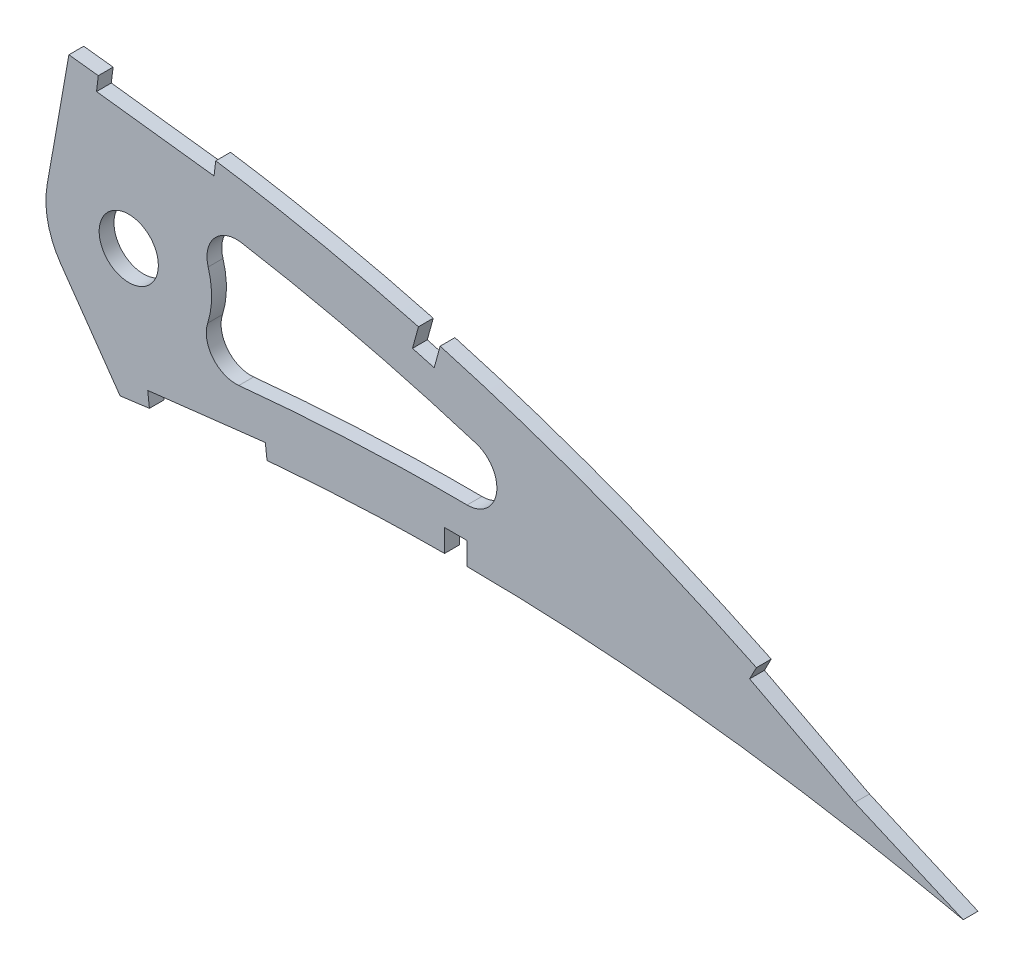
SolidWorks part; units mm, degrees
material "Plywood"
ref_plane "Front Plane" through (0, 0, 0) normal (0, 0, 1) x (1, 0, 0)
ref_plane "Top Plane" through (0, 0, 0) normal (0, 1, 0) x (1, 0, 0)
ref_plane "Right Plane" through (0, 0, 0) normal (1, 0, 0) x (0, 0, -1)
curve "Curve1"
  spline degree 3 poles (554.3197, 0.8642, 0) (554.2772, 0.8904, 0) (554.1075, 0.9953, 0) (553.7252, 1.2298, 0) (553.0885, 1.6204, 0) (552.1972, 2.1644, 0) (551.0519, 2.8603, 0) (549.6522, 3.7033, 0) (547.9988, 4.6906, 0) (546.0922, 5.8176, 0) (543.9326, 7.0789, 0) (541.5207, 8.4695, 0) (538.8569, 9.9815, 0) (535.942, 11.6087, 0) (532.7772, 13.3434, 0) (529.3631, 15.1777, 0) (525.7007, 17.1023, 0) (521.7917, 19.109, 0) (517.6366, 21.1866, 0) (513.2374, 23.3265, 0) (508.5956, 25.518, 0) (503.7128, 27.7495, 0) (498.5918, 30.0118, 0) (493.234, 32.2909, 0) (487.6424, 34.577, 0) (481.8195, 36.8569, 0) (475.7686, 39.1203, 0) (469.4922, 41.3526, 0) (462.9949, 43.5439, 0) (456.2798, 45.6802, 0) (449.3518, 47.7496, 0) (442.2149, 49.739, 0) (434.875, 51.6379, 0) (427.3368, 53.4327, 0) (419.6066, 55.1112, 0) (411.6907, 56.6635, 0) (403.5957, 58.0739, 0) (395.344, 59.3415, 0) (387.0683, 60.3958, 0) (378.8096, 61.4299, 0) (370.5633, 62.4014, 0) (362.2161, 63.3317, 0) (353.7762, 64.2156, 0) (345.252, 65.0503, 0) (336.6519, 65.8323, 0) (327.9851, 66.5592, 0) (319.2598, 67.227, 0) (310.4852, 67.8346, 0) (301.6702, 68.3766, 0) (292.8239, 68.8527, 0) (283.9555, 69.2595, 0) (275.0741, 69.5943, 0) (266.1892, 69.8549, 0) (257.3099, 70.039, 0) (248.446, 70.1454, 0) (239.6066, 70.171, 0) (230.8014, 70.1156, 0) (222.0395, 69.9772, 0) (213.3305, 69.7538, 0) (204.6838, 69.4452, 0) (196.1087, 69.0513, 0) (187.6145, 68.5689, 0) (179.2105, 68.0012, 0) (170.9059, 67.3456, 0) (162.7101, 66.6021, 0) (154.6315, 65.7736, 0) (146.6791, 64.8581, 0) (138.8614, 63.858, 0) (131.1871, 62.7754, 0) (123.6647, 61.6096, 0) (116.3022, 60.3641, 0) (109.1077, 59.04, 0) (102.0887, 57.6413, 0) (95.2529, 56.1683, 0) (88.6074, 54.6255, 0) (82.1593, 53.0155, 0) (75.9155, 51.3413, 0) (69.8822, 49.607, 0) (64.0656, 47.8163, 0) (58.4725, 45.9714, 0) (53.107, 44.0792, 0) (47.9758, 42.141, 0) (43.0829, 40.1629, 0) (38.4338, 38.1474, 0) (34.0322, 36.1008, 0) (29.883, 34.0255, 0) (25.9891, 31.9271, 0) (22.3545, 29.809, 0) (18.9827, 27.675, 0) (15.875, 25.5306, 0) (13.0358, 23.3771, 0) (10.4661, 21.22, 0) (8.1674, 19.0625, 0) (6.143, 16.9061, 0) (4.3929, 14.7547, 0) (2.9194, 12.6099, 0) (1.7228, 10.4738, 0) (0.8056, 8.3479, 0) (0.1671, 6.2334, 0) (-0.1824, 4.1334, 0) (-0.2694, 2.0463, 0) (-0.0897, 0.6811, 0) (0, 0, 0) knots 0 0 0 0 0.000254 0.001015 0.002283 0.004057 0.006331 0.009105 0.012374 0.016134 0.02038 0.025106 0.030306 0.035972 0.0421 0.048678 0.055702 0.06316 0.071046 0.07935 0.088063 0.097176 0.106678 0.116562 0.126814 0.137428 0.148394 0.1597 0.171338 0.183298 0.19557 0.208144 0.221012 0.234162 0.247587 0.261277 0.275223 0.289414 0.303771 0.317689 0.331784 0.34604 0.360444 0.374983 0.38964 0.404403 0.419257 0.434187 0.449177 0.464215 0.479284 0.49437 0.509458 0.524532 0.539579 0.554583 0.56953 0.584403 0.599191 0.613877 0.628447 0.642889 0.657186 0.671326 0.685294 0.699078 0.712665 0.726043 0.739198 0.752118 0.764792 0.777208 0.789356 0.801224 0.812804 0.824083 0.835055 0.84571 0.856038 0.866034 0.875689 0.884998 0.893953 0.902553 0.910789 0.918661 0.926166 0.933303 0.940071 0.946475 0.952518 0.958205 0.963547 0.968557 0.97325 0.977651 0.981787 0.985694 0.989415 0.993001 0.996508 1 1 1 1
curve "Curve2"
  spline degree 3 poles (0, 0, 0) (0.1423, -0.672, 0) (0.4277, -2.019, 0) (1.203, -3.9582, 0) (2.2282, -5.8223, 0) (3.5249, -7.6064, 0) (5.0845, -9.31, 0) (6.9036, -10.9348, 0) (8.9803, -12.4801, 0) (11.3119, -13.945, 0) (13.8951, -15.3312, 0) (16.7269, -16.6378, 0) (19.8048, -17.8643, 0) (23.1254, -19.0092, 0) (26.6846, -20.0741, 0) (30.4791, -21.0566, 0) (34.5045, -21.9578, 0) (38.7571, -22.7757, 0) (43.232, -23.5109, 0) (47.9248, -24.1631, 0) (52.8305, -24.7327, 0) (57.9444, -25.2185, 0) (63.2614, -25.6215, 0) (68.7762, -25.942, 0) (74.4834, -26.1811, 0) (80.3777, -26.3377, 0) (86.4531, -26.4144, 0) (92.7043, -26.4123, 0) (99.1251, -26.3308, 0) (105.71, -26.1745, 0) (112.4527, -25.9423, 0) (119.3471, -25.6371, 0) (126.387, -25.2619, 0) (133.5661, -24.818, 0) (140.8781, -24.3074, 0) (148.3166, -23.7341, 0) (155.8748, -23.0997, 0) (163.5462, -22.4077, 0) (171.324, -21.6617, 0) (179.2015, -20.864, 0) (187.1716, -20.0183, 0) (195.2274, -19.1275, 0) (203.3619, -18.1963, 0) (211.5677, -17.2262, 0) (219.8379, -16.223, 0) (228.1647, -15.1885, 0) (236.5412, -14.1266, 0) (244.9597, -13.0425, 0) (253.4125, -11.9359, 0) (261.8924, -10.8148, 0) (270.3912, -9.6781, 0) (278.9016, -8.5319, 0) (287.4156, -7.3796, 0) (295.925, -6.2216, 0) (304.4222, -5.0626, 0) (312.8995, -3.9059, 0) (321.3485, -2.7516, 0) (329.7616, -1.6054, 0) (338.1302, -0.4672, 0) (346.4467, 0.6607, 0) (354.7031, 1.775, 0) (362.8916, 2.8743, 0) (371.0037, 3.9578, 0) (379.0314, 5.0259, 0) (386.8463, 6.0463, 0) (394.4281, 7.0733, 0) (401.8022, 7.9152, 0) (409.0845, 8.6338, 0) (416.2825, 9.2229, 0) (423.3877, 9.6911, 0) (430.3918, 10.0417, 0) (437.2865, 10.2795, 0) (444.0631, 10.4116, 0) (450.7132, 10.4414, 0) (457.2276, 10.3785, 0) (463.598, 10.2277, 0) (469.8153, 9.9961, 0) (475.8709, 9.6912, 0) (481.7563, 9.3216, 0) (487.4626, 8.8925, 0) (492.9818, 8.4141, 0) (498.3055, 7.8933, 0) (503.4254, 7.336, 0) (508.334, 6.7541, 0) (513.0236, 6.1512, 0) (517.4871, 5.5374, 0) (521.7172, 4.9187, 0) (525.7074, 4.3032, 0) (529.4512, 3.6966, 0) (532.9427, 3.1071, 0) (536.1764, 2.5402, 0) (539.1467, 2.0013, 0) (541.8495, 1.4973, 0) (544.2794, 1.0307, 0) (546.4331, 0.6092, 0) (548.3068, 0.2346, 0) (549.8976, -0.0878, 0) (551.2027, -0.3567, 0) (552.2202, -0.5677, 0) (552.948, -0.7211, 0) (553.3854, -0.8124, 0) (553.5798, -0.8538, 0) (553.6283, -0.8642, 0) knots 0 0 0 0 0.003638 0.007293 0.011028 0.014901 0.018963 0.023258 0.027821 0.032679 0.037853 0.043362 0.049215 0.055422 0.061989 0.068918 0.076211 0.083868 0.091887 0.100266 0.109 0.118085 0.127515 0.137285 0.147388 0.157816 0.168563 0.179619 0.190977 0.202627 0.21456 0.226767 0.239236 0.251959 0.264924 0.27812 0.291536 0.30516 0.318981 0.332985 0.347163 0.361499 0.375981 0.390597 0.405333 0.420175 0.43511 0.450124 0.465203 0.480333 0.495501 0.51069 0.525887 0.541078 0.556247 0.571382 0.586466 0.601485 0.616424 0.631269 0.646007 0.660621 0.675098 0.689423 0.703582 0.716908 0.730009 0.742952 0.755726 0.76832 0.780724 0.792927 0.804916 0.816679 0.828204 0.839475 0.850481 0.861208 0.871639 0.881763 0.891564 0.901027 0.910139 0.918884 0.927249 0.935221 0.942785 0.949928 0.956638 0.962904 0.968712 0.974054 0.978918 0.983297 0.98718 0.990561 0.993433 0.995791 0.99763 0.998946 0.999737 1 1 1 1
sketch "Sketch1" plane through (0, 0, 0) normal (0, 0, 1) x (1, 0, 0)
  line L28 (0, 63.5) -> (-23.1981, 63.5) construction
  line L39 (379.9183, -27.3345) -> (379.9183, 27.3345) construction
  line L40 (379.9183, 61.2846) -> (364.3182, 3.0643) construction
  line L41 (554.3197, 0.8642) -> (558.9578, -2.001)
  line L42 (553.6283, -0.8642) -> (558.9578, -2.001)
  circle A0 centre (68.58, 6.35) radius 9.525 construction
  circle A1 centre (246.38, 6.35) radius 9.525 construction
  spline S2 degree 3 poles (-1940.5458, -482.1449) (50.3561, 59.7807) (-7.8624, 18.7173) (1.203, -3.9582) (2.2282, -5.8223) (3.5249, -7.6064) (5.0845, -9.31) (6.9036, -10.9348) (8.9803, -12.4801) (11.3119, -13.945) (13.8951, -15.3312) (16.7269, -16.6378) (19.8048, -17.8643) (23.1254, -19.0092) (26.6846, -20.0741) (30.4791, -21.0566) (34.5045, -21.9578) (38.7571, -22.7757) (43.232, -23.5109) (47.9248, -24.1631) (52.8305, -24.7327) (57.9444, -25.2185) (63.2614, -25.6215) (68.7762, -25.942) (74.4834, -26.1811) (80.3777, -26.3377) (86.4531, -26.4144) (92.7043, -26.4123) (99.1251, -26.3308) (105.71, -26.1745) (112.4527, -25.9423) (119.3471, -25.6371) (126.387, -25.2619) (133.5661, -24.818) (140.8781, -24.3074) (148.3166, -23.7341) (155.8748, -23.0997) (163.5462, -22.4077) (171.324, -21.6617) (179.2015, -20.864) (187.1716, -20.0183) (195.2274, -19.1275) (203.3619, -18.1963) (211.5677, -17.2262) (219.8379, -16.223) (228.1647, -15.1885) (236.5412, -14.1266) (244.9597, -13.0425) (253.4125, -11.9359) (261.8924, -10.8148) (270.3912, -9.6781) (278.9016, -8.5319) (287.4156, -7.3796) (295.925, -6.2216) (304.4222, -5.0626) (312.8995, -3.9059) (321.3485, -2.7516) (329.7616, -1.6054) (338.1302, -0.4672) (346.4467, 0.6607) (354.7031, 1.775) (362.8916, 2.8743) (371.0037, 3.9578) (379.0314, 5.0259) (386.8463, 6.0463) (394.4281, 7.0733) (401.8022, 7.9152) (409.0845, 8.6338) (416.2825, 9.2229) (423.3877, 9.6911) (430.3918, 10.0417) (437.2865, 10.2795) (444.0631, 10.4116) (450.7132, 10.4414) (457.2276, 10.3785) (463.598, 10.2277) (469.8153, 9.9961) (475.8709, 9.6912) (481.7563, 9.3216) (487.4626, 8.8925) (492.9818, 8.4141) (498.3055, 7.8933) (503.4254, 7.336) (508.334, 6.7541) (513.0236, 6.1512) (517.4871, 5.5374) (521.7172, 4.9187) (525.7074, 4.3032) (529.4512, 3.6966) (532.9427, 3.1071) (536.1764, 2.5402) (539.1467, 2.0013) (541.8495, 1.4973) (544.2794, 1.0307) (546.4331, 0.6092) (548.3068, 0.2346) (549.8976, -0.0878) (551.2027, -0.3567) (552.2202, -0.5677) (552.948, -0.7211) (569.5328, -4.1827) (584.5994, -13.6239) (1015.6751, 1944.7152) knots -0.117928 -0.117928 -0.117928 -0.117928 0.003638 0.007293 0.011028 0.014901 0.018963 0.023258 0.027821 0.032679 0.037853 0.043362 0.049215 0.055422 0.061989 0.068918 0.076211 0.083868 0.091887 0.100266 0.109 0.118085 0.127515 0.137285 0.147388 0.157816 0.168563 0.179619 0.190977 0.202627 0.21456 0.226767 0.239236 0.251959 0.264924 0.27812 0.291536 0.30516 0.318981 0.332985 0.347163 0.361499 0.375981 0.390597 0.405333 0.420175 0.43511 0.450124 0.465203 0.480333 0.495501 0.51069 0.525887 0.541078 0.556247 0.571382 0.586466 0.601485 0.616424 0.631269 0.646007 0.660621 0.675098 0.689423 0.703582 0.716908 0.730009 0.742952 0.755726 0.76832 0.780724 0.792927 0.804916 0.816679 0.828204 0.839475 0.850481 0.861208 0.871639 0.881763 0.891564 0.901027 0.910139 0.918884 0.927249 0.935221 0.942785 0.949928 0.956638 0.962904 0.968712 0.974054 0.978918 0.983297 0.98718 0.990561 0.993433 0.995791 0.99763 0.998946 0.999737 1.087506 1.087506 1.087506 1.087506 only from (0, 0) to (553.6283, -0.8642) construction
  spline S3 degree 3 poles (0, 0) (0.1423, -0.672) (0.4277, -2.019) (1.203, -3.9582) (2.2282, -5.8223) (3.5249, -7.6064) (5.0845, -9.31) (6.9036, -10.9348) (8.9803, -12.4801) (11.3119, -13.945) (13.8951, -15.3312) (16.7269, -16.6378) (19.8048, -17.8643) (23.1254, -19.0092) (26.6846, -20.0741) (30.4791, -21.0566) (34.5045, -21.9578) (38.7571, -22.7757) (43.232, -23.5109) (47.9248, -24.1631) (52.8305, -24.7327) (57.9444, -25.2185) (63.2614, -25.6215) (68.7762, -25.942) (74.4834, -26.1811) (80.3777, -26.3377) (86.4531, -26.4144) (92.7043, -26.4123) (99.1251, -26.3308) (105.71, -26.1745) (112.4527, -25.9423) (119.3471, -25.6371) (126.387, -25.2619) (133.5661, -24.818) (140.8781, -24.3074) (148.3166, -23.7341) (155.8748, -23.0997) (163.5462, -22.4077) (171.324, -21.6617) (179.2015, -20.864) (187.1716, -20.0183) (195.2274, -19.1275) (203.3619, -18.1963) (211.5677, -17.2262) (219.8379, -16.223) (228.1647, -15.1885) (236.5412, -14.1266) (244.9597, -13.0425) (253.4125, -11.9359) (261.8924, -10.8148) (270.3912, -9.6781) (278.9016, -8.5319) (287.4156, -7.3796) (295.925, -6.2216) (304.4222, -5.0626) (312.8995, -3.9059) (321.3485, -2.7516) (329.7616, -1.6054) (338.1302, -0.4672) (346.4467, 0.6607) (354.7031, 1.775) (362.8916, 2.8743) (371.0037, 3.9578) (379.0314, 5.0259) (386.8463, 6.0463) (394.4281, 7.0733) (401.8022, 7.9152) (409.0845, 8.6338) (416.2825, 9.2229) (423.3877, 9.6911) (430.3918, 10.0417) (437.2865, 10.2795) (444.0631, 10.4116) (450.7132, 10.4414) (457.2276, 10.3785) (463.598, 10.2277) (469.8153, 9.9961) (475.8709, 9.6912) (481.7563, 9.3216) (487.4626, 8.8925) (492.9818, 8.4141) (498.3055, 7.8933) (503.4254, 7.336) (508.334, 6.7541) (513.0236, 6.1512) (517.4871, 5.5374) (521.7172, 4.9187) (525.7074, 4.3032) (529.4512, 3.6966) (532.9427, 3.1071) (536.1764, 2.5402) (539.1467, 2.0013) (541.8495, 1.4973) (544.2794, 1.0307) (546.4331, 0.6092) (548.3068, 0.2346) (549.8976, -0.0878) (551.2027, -0.3567) (552.2202, -0.5677) (552.948, -0.7211) (553.3854, -0.8124) (553.5798, -0.8538) (553.6283, -0.8642) knots 0 0 0 0 0.003638 0.007293 0.011028 0.014901 0.018963 0.023258 0.027821 0.032679 0.037853 0.043362 0.049215 0.055422 0.061989 0.068918 0.076211 0.083868 0.091887 0.100266 0.109 0.118085 0.127515 0.137285 0.147388 0.157816 0.168563 0.179619 0.190977 0.202627 0.21456 0.226767 0.239236 0.251959 0.264924 0.27812 0.291536 0.30516 0.318981 0.332985 0.347163 0.361499 0.375981 0.390597 0.405333 0.420175 0.43511 0.450124 0.465203 0.480333 0.495501 0.51069 0.525887 0.541078 0.556247 0.571382 0.586466 0.601485 0.616424 0.631269 0.646007 0.660621 0.675098 0.689423 0.703582 0.716908 0.730009 0.742952 0.755726 0.76832 0.780724 0.792927 0.804916 0.816679 0.828204 0.839475 0.850481 0.861208 0.871639 0.881763 0.891564 0.901027 0.910139 0.918884 0.927249 0.935221 0.942785 0.949928 0.956638 0.962904 0.968712 0.974054 0.978918 0.983297 0.98718 0.990561 0.993433 0.995791 0.99763 0.998946 0.999737 1 1 1 1
  spline S4 degree 3 poles (1649.7869, 1673.5394) (582.8314, -23.1055) (569.8335, -8.6508) (553.7252, 1.2298) (553.0885, 1.6204) (552.1972, 2.1644) (551.0519, 2.8603) (549.6522, 3.7033) (547.9988, 4.6906) (546.0922, 5.8176) (543.9326, 7.0789) (541.5207, 8.4695) (538.8569, 9.9815) (535.942, 11.6087) (532.7772, 13.3434) (529.3631, 15.1777) (525.7007, 17.1023) (521.7917, 19.109) (517.6366, 21.1866) (513.2374, 23.3265) (508.5956, 25.518) (503.7128, 27.7495) (498.5918, 30.0118) (493.234, 32.2909) (487.6424, 34.577) (481.8195, 36.8569) (475.7686, 39.1203) (469.4922, 41.3526) (462.9949, 43.5439) (456.2798, 45.6802) (449.3518, 47.7496) (442.2149, 49.739) (434.875, 51.6379) (427.3368, 53.4327) (419.6066, 55.1112) (411.6907, 56.6635) (403.5957, 58.0739) (395.344, 59.3415) (387.0683, 60.3958) (378.8096, 61.4299) (370.5633, 62.4014) (362.2161, 63.3317) (353.7762, 64.2156) (345.252, 65.0503) (336.6519, 65.8323) (327.9851, 66.5592) (319.2598, 67.227) (310.4852, 67.8346) (301.6702, 68.3766) (292.8239, 68.8527) (283.9555, 69.2595) (275.0741, 69.5943) (266.1892, 69.8549) (257.3099, 70.039) (248.446, 70.1454) (239.6066, 70.171) (230.8014, 70.1156) (222.0395, 69.9772) (213.3305, 69.7538) (204.6838, 69.4452) (196.1087, 69.0513) (187.6145, 68.5689) (179.2105, 68.0012) (170.9059, 67.3456) (162.7101, 66.6021) (154.6315, 65.7736) (146.6791, 64.8581) (138.8614, 63.858) (131.1871, 62.7754) (123.6647, 61.6096) (116.3022, 60.3641) (109.1077, 59.04) (102.0887, 57.6413) (95.2529, 56.1683) (88.6074, 54.6255) (82.1593, 53.0155) (75.9155, 51.3413) (69.8822, 49.607) (64.0656, 47.8163) (58.4725, 45.9714) (53.107, 44.0792) (47.9758, 42.141) (43.0829, 40.1629) (38.4338, 38.1474) (34.0322, 36.1008) (29.883, 34.0255) (25.9891, 31.9271) (22.3545, 29.809) (18.9827, 27.675) (15.875, 25.5306) (13.0358, 23.3771) (10.4661, 21.22) (8.1674, 19.0625) (6.143, 16.9061) (4.3929, 14.7547) (2.9194, 12.6099) (1.7228, 10.4738) (0.8056, 8.3479) (0.1671, 6.2334) (-0.1824, 4.1334) (-1.1977, -20.225) (67.5062, -39.5284) (-1990.2908, -190.8143) knots -0.093914 -0.093914 -0.093914 -0.093914 0.000254 0.001015 0.002283 0.004057 0.006331 0.009105 0.012374 0.016134 0.02038 0.025106 0.030306 0.035972 0.0421 0.048678 0.055702 0.06316 0.071046 0.07935 0.088063 0.097176 0.106678 0.116562 0.126814 0.137428 0.148394 0.1597 0.171338 0.183298 0.19557 0.208144 0.221012 0.234162 0.247587 0.261277 0.275223 0.289414 0.303771 0.317689 0.331784 0.34604 0.360444 0.374983 0.38964 0.404403 0.419257 0.434187 0.449177 0.464215 0.479284 0.49437 0.509458 0.524532 0.539579 0.554583 0.56953 0.584403 0.599191 0.613877 0.628447 0.642889 0.657186 0.671326 0.685294 0.699078 0.712665 0.726043 0.739198 0.752118 0.764792 0.777208 0.789356 0.801224 0.812804 0.824083 0.835055 0.84571 0.856038 0.866034 0.875689 0.884998 0.893953 0.902553 0.910789 0.918661 0.926166 0.933303 0.940071 0.946475 0.952518 0.958205 0.963547 0.968557 0.97325 0.977651 0.981787 0.985694 0.989415 0.993001 0.996508 1.11295 1.11295 1.11295 1.11295 only from (554.3197, 0.8642) to (0, 0) construction
  spline S6 degree 3 poles (554.3197, 0.8642) (554.2772, 0.8904) (554.1075, 0.9953) (553.7252, 1.2298) (553.0885, 1.6204) (552.1972, 2.1644) (551.0519, 2.8603) (549.6522, 3.7033) (547.9988, 4.6906) (546.0922, 5.8176) (543.9326, 7.0789) (541.5207, 8.4695) (538.8569, 9.9815) (535.942, 11.6087) (532.7772, 13.3434) (529.3631, 15.1777) (525.7007, 17.1023) (521.7917, 19.109) (517.6366, 21.1866) (513.2374, 23.3265) (508.5956, 25.518) (503.7128, 27.7495) (498.5918, 30.0118) (493.234, 32.2909) (487.6424, 34.577) (481.8195, 36.8569) (475.7686, 39.1203) (469.4922, 41.3526) (462.9949, 43.5439) (456.2798, 45.6802) (449.3518, 47.7496) (442.2149, 49.739) (434.875, 51.6379) (427.3368, 53.4327) (419.6066, 55.1112) (411.6907, 56.6635) (403.5957, 58.0739) (395.344, 59.3415) (387.0683, 60.3958) (378.8096, 61.4299) (370.5633, 62.4014) (362.2161, 63.3317) (353.7762, 64.2156) (345.252, 65.0503) (336.6519, 65.8323) (327.9851, 66.5592) (319.2598, 67.227) (310.4852, 67.8346) (301.6702, 68.3766) (292.8239, 68.8527) (283.9555, 69.2595) (275.0741, 69.5943) (266.1892, 69.8549) (257.3099, 70.039) (248.446, 70.1454) (239.6066, 70.171) (230.8014, 70.1156) (222.0395, 69.9772) (213.3305, 69.7538) (204.6838, 69.4452) (196.1087, 69.0513) (187.6145, 68.5689) (179.2105, 68.0012) (170.9059, 67.3456) (162.7101, 66.6021) (154.6315, 65.7736) (146.6791, 64.8581) (138.8614, 63.858) (131.1871, 62.7754) (123.6647, 61.6096) (116.3022, 60.3641) (109.1077, 59.04) (102.0887, 57.6413) (95.2529, 56.1683) (88.6074, 54.6255) (82.1593, 53.0155) (75.9155, 51.3413) (69.8822, 49.607) (64.0656, 47.8163) (58.4725, 45.9714) (53.107, 44.0792) (47.9758, 42.141) (43.0829, 40.1629) (38.4338, 38.1474) (34.0322, 36.1008) (29.883, 34.0255) (25.9891, 31.9271) (22.3545, 29.809) (18.9827, 27.675) (15.875, 25.5306) (13.0358, 23.3771) (10.4661, 21.22) (8.1674, 19.0625) (6.143, 16.9061) (4.3929, 14.7547) (2.9194, 12.6099) (1.7228, 10.4738) (0.8056, 8.3479) (0.1671, 6.2334) (-0.1824, 4.1334) (-0.2694, 2.0463) (-0.0897, 0.6811) (0, 0) knots 0 0 0 0 0.000254 0.001015 0.002283 0.004057 0.006331 0.009105 0.012374 0.016134 0.02038 0.025106 0.030306 0.035972 0.0421 0.048678 0.055702 0.06316 0.071046 0.07935 0.088063 0.097176 0.106678 0.116562 0.126814 0.137428 0.148394 0.1597 0.171338 0.183298 0.19557 0.208144 0.221012 0.234162 0.247587 0.261277 0.275223 0.289414 0.303771 0.317689 0.331784 0.34604 0.360444 0.374983 0.38964 0.404403 0.419257 0.434187 0.449177 0.464215 0.479284 0.49437 0.509458 0.524532 0.539579 0.554583 0.56953 0.584403 0.599191 0.613877 0.628447 0.642889 0.657186 0.671326 0.685294 0.699078 0.712665 0.726043 0.739198 0.752118 0.764792 0.777208 0.789356 0.801224 0.812804 0.824083 0.835055 0.84571 0.856038 0.866034 0.875689 0.884998 0.893953 0.902553 0.910789 0.918661 0.926166 0.933303 0.940071 0.946475 0.952518 0.958205 0.963547 0.968557 0.97325 0.977651 0.981787 0.985694 0.989415 0.993001 0.996508 1 1 1 1
  point P10 (81.0487, 17.1134)
  point P11 (234.9492, 33.5094)
  dimension "D2" = 19.05
  dimension "D18" = 177.8
  dimension "D3" = 15
  dimension "D5" = 63.5
  dimension "D7" = 57.15
  dimension "D12" = 57.15
  dimension "D17" = 68.58
extrude "Boss-Extrude1" add sketch "Sketch1" along normal blind 3.175
sketch "Sketch2" plane through (0, 0, 3.175) normal (0, 0, 1) x (1, 0, 0)
  line L0 (362.4084, 36.32) -> (367.0753, 62.7877)
  line L5 (365.3537, 23.0344) -> (378.0559, 4.8939)
  line L6 (379.9183, 33.2326) -> (412.5731, 33.2326) construction
  circle A4 centre (379.9183, 33.2326) radius 17.78
  circle A10 centre (379.9183, 33.2326) radius 6.35
  spline S0 degree 3 poles (-1940.5458, -482.1449) (50.3561, 59.7807) (-7.8624, 18.7173) (1.203, -3.9582) (2.2282, -5.8223) (3.5249, -7.6064) (5.0845, -9.31) (6.9036, -10.9348) (8.9803, -12.4801) (11.3119, -13.945) (13.8951, -15.3312) (16.7269, -16.6378) (19.8048, -17.8643) (23.1254, -19.0092) (26.6846, -20.0741) (30.4791, -21.0566) (34.5045, -21.9578) (38.7571, -22.7757) (43.232, -23.5109) (47.9248, -24.1631) (52.8305, -24.7327) (57.9444, -25.2185) (63.2614, -25.6215) (68.7762, -25.942) (74.4834, -26.1811) (80.3777, -26.3377) (86.4531, -26.4144) (92.7043, -26.4123) (99.1251, -26.3308) (105.71, -26.1745) (112.4527, -25.9423) (119.3471, -25.6371) (126.387, -25.2619) (133.5661, -24.818) (140.8781, -24.3074) (148.3166, -23.7341) (155.8748, -23.0997) (163.5462, -22.4077) (171.324, -21.6617) (179.2015, -20.864) (187.1716, -20.0183) (195.2274, -19.1275) (203.3619, -18.1963) (211.5677, -17.2262) (219.8379, -16.223) (228.1647, -15.1885) (236.5412, -14.1266) (244.9597, -13.0425) (253.4125, -11.9359) (261.8924, -10.8148) (270.3912, -9.6781) (278.9016, -8.5319) (287.4156, -7.3796) (295.925, -6.2216) (304.4222, -5.0626) (312.8995, -3.9059) (321.3485, -2.7516) (329.7616, -1.6054) (338.1302, -0.4672) (346.4467, 0.6607) (354.7031, 1.775) (362.8916, 2.8743) (371.0037, 3.9578) (379.0314, 5.0259) (386.8463, 6.0463) (394.4281, 7.0733) (401.8022, 7.9152) (409.0845, 8.6338) (416.2825, 9.2229) (423.3877, 9.6911) (430.3918, 10.0417) (437.2865, 10.2795) (444.0631, 10.4116) (450.7132, 10.4414) (457.2276, 10.3785) (463.598, 10.2277) (469.8153, 9.9961) (475.8709, 9.6912) (481.7563, 9.3216) (487.4626, 8.8925) (492.9818, 8.4141) (498.3055, 7.8933) (503.4254, 7.336) (508.334, 6.7541) (513.0236, 6.1512) (517.4871, 5.5374) (521.7172, 4.9187) (525.7074, 4.3032) (529.4512, 3.6966) (532.9427, 3.1071) (536.1764, 2.5402) (539.1467, 2.0013) (541.8495, 1.4973) (544.2794, 1.0307) (546.4331, 0.6092) (548.3068, 0.2346) (549.8976, -0.0878) (551.2027, -0.3567) (552.2202, -0.5677) (552.948, -0.7211) (569.5328, -4.1827) (584.5994, -13.6239) (1015.6751, 1944.7152) knots -0.117928 -0.117928 -0.117928 -0.117928 0.003638 0.007293 0.011028 0.014901 0.018963 0.023258 0.027821 0.032679 0.037853 0.043362 0.049215 0.055422 0.061989 0.068918 0.076211 0.083868 0.091887 0.100266 0.109 0.118085 0.127515 0.137285 0.147388 0.157816 0.168563 0.179619 0.190977 0.202627 0.21456 0.226767 0.239236 0.251959 0.264924 0.27812 0.291536 0.30516 0.318981 0.332985 0.347163 0.361499 0.375981 0.390597 0.405333 0.420175 0.43511 0.450124 0.465203 0.480333 0.495501 0.51069 0.525887 0.541078 0.556247 0.571382 0.586466 0.601485 0.616424 0.631269 0.646007 0.660621 0.675098 0.689423 0.703582 0.716908 0.730009 0.742952 0.755726 0.76832 0.780724 0.792927 0.804916 0.816679 0.828204 0.839475 0.850481 0.861208 0.871639 0.881763 0.891564 0.901027 0.910139 0.918884 0.927249 0.935221 0.942785 0.949928 0.956638 0.962904 0.968712 0.974054 0.978918 0.983297 0.98718 0.990561 0.993433 0.995791 0.99763 0.998946 0.999737 1.087506 1.087506 1.087506 1.087506 only from (0, 0) to (553.6283, -0.8642) construction
  spline S1 degree 3 poles (1649.7869, 1673.5394) (582.8314, -23.1055) (569.8335, -8.6508) (553.7252, 1.2298) (553.0885, 1.6204) (552.1972, 2.1644) (551.0519, 2.8603) (549.6522, 3.7033) (547.9988, 4.6906) (546.0922, 5.8176) (543.9326, 7.0789) (541.5207, 8.4695) (538.8569, 9.9815) (535.942, 11.6087) (532.7772, 13.3434) (529.3631, 15.1777) (525.7007, 17.1023) (521.7917, 19.109) (517.6366, 21.1866) (513.2374, 23.3265) (508.5956, 25.518) (503.7128, 27.7495) (498.5918, 30.0118) (493.234, 32.2909) (487.6424, 34.577) (481.8195, 36.8569) (475.7686, 39.1203) (469.4922, 41.3526) (462.9949, 43.5439) (456.2798, 45.6802) (449.3518, 47.7496) (442.2149, 49.739) (434.875, 51.6379) (427.3368, 53.4327) (419.6066, 55.1112) (411.6907, 56.6635) (403.5957, 58.0739) (395.344, 59.3415) (387.0683, 60.3958) (378.8096, 61.4299) (370.5633, 62.4014) (362.2161, 63.3317) (353.7762, 64.2156) (345.252, 65.0503) (336.6519, 65.8323) (327.9851, 66.5592) (319.2598, 67.227) (310.4852, 67.8346) (301.6702, 68.3766) (292.8239, 68.8527) (283.9555, 69.2595) (275.0741, 69.5943) (266.1892, 69.8549) (257.3099, 70.039) (248.446, 70.1454) (239.6066, 70.171) (230.8014, 70.1156) (222.0395, 69.9772) (213.3305, 69.7538) (204.6838, 69.4452) (196.1087, 69.0513) (187.6145, 68.5689) (179.2105, 68.0012) (170.9059, 67.3456) (162.7101, 66.6021) (154.6315, 65.7736) (146.6791, 64.8581) (138.8614, 63.858) (131.1871, 62.7754) (123.6647, 61.6096) (116.3022, 60.3641) (109.1077, 59.04) (102.0887, 57.6413) (95.2529, 56.1683) (88.6074, 54.6255) (82.1593, 53.0155) (75.9155, 51.3413) (69.8822, 49.607) (64.0656, 47.8163) (58.4725, 45.9714) (53.107, 44.0792) (47.9758, 42.141) (43.0829, 40.1629) (38.4338, 38.1474) (34.0322, 36.1008) (29.883, 34.0255) (25.9891, 31.9271) (22.3545, 29.809) (18.9827, 27.675) (15.875, 25.5306) (13.0358, 23.3771) (10.4661, 21.22) (8.1674, 19.0625) (6.143, 16.9061) (4.3929, 14.7547) (2.9194, 12.6099) (1.7228, 10.4738) (0.8056, 8.3479) (0.1671, 6.2334) (-0.1824, 4.1334) (-1.1977, -20.225) (67.5062, -39.5284) (-1990.2908, -190.8143) knots -0.093914 -0.093914 -0.093914 -0.093914 0.000254 0.001015 0.002283 0.004057 0.006331 0.009105 0.012374 0.016134 0.02038 0.025106 0.030306 0.035972 0.0421 0.048678 0.055702 0.06316 0.071046 0.07935 0.088063 0.097176 0.106678 0.116562 0.126814 0.137428 0.148394 0.1597 0.171338 0.183298 0.19557 0.208144 0.221012 0.234162 0.247587 0.261277 0.275223 0.289414 0.303771 0.317689 0.331784 0.34604 0.360444 0.374983 0.38964 0.404403 0.419257 0.434187 0.449177 0.464215 0.479284 0.49437 0.509458 0.524532 0.539579 0.554583 0.56953 0.584403 0.599191 0.613877 0.628447 0.642889 0.657186 0.671326 0.685294 0.699078 0.712665 0.726043 0.739198 0.752118 0.764792 0.777208 0.789356 0.801224 0.812804 0.824083 0.835055 0.84571 0.856038 0.866034 0.875689 0.884998 0.893953 0.902553 0.910789 0.918661 0.926166 0.933303 0.940071 0.946475 0.952518 0.958205 0.963547 0.968557 0.97325 0.977651 0.981787 0.985694 0.989415 0.993001 0.996508 1.11295 1.11295 1.11295 1.11295 only from (554.3197, 0.8642) to (0, 0) construction
  spline S2 degree 3 poles (0, 0) (0.1423, -0.672) (0.4277, -2.019) (1.203, -3.9582) (2.2282, -5.8223) (3.5249, -7.6064) (5.0845, -9.31) (6.9036, -10.9348) (8.9803, -12.4801) (11.3119, -13.945) (13.8951, -15.3312) (16.7269, -16.6378) (19.8048, -17.8643) (23.1254, -19.0092) (26.6846, -20.0741) (30.4791, -21.0566) (34.5045, -21.9578) (38.7571, -22.7757) (43.232, -23.5109) (47.9248, -24.1631) (52.8305, -24.7327) (57.9444, -25.2185) (63.2614, -25.6215) (68.7762, -25.942) (74.4834, -26.1811) (80.3777, -26.3377) (86.4531, -26.4144) (92.7043, -26.4123) (99.1251, -26.3308) (105.71, -26.1745) (112.4527, -25.9423) (119.3471, -25.6371) (126.387, -25.2619) (133.5661, -24.818) (140.8781, -24.3074) (148.3166, -23.7341) (155.8748, -23.0997) (163.5462, -22.4077) (171.324, -21.6617) (179.2015, -20.864) (187.1716, -20.0183) (195.2274, -19.1275) (203.3619, -18.1963) (211.5677, -17.2262) (219.8379, -16.223) (228.1647, -15.1885) (236.5412, -14.1266) (244.9597, -13.0425) (253.4125, -11.9359) (261.8924, -10.8148) (270.3912, -9.6781) (278.9016, -8.5319) (287.4156, -7.3796) (295.925, -6.2216) (304.4222, -5.0626) (312.8995, -3.9059) (321.3485, -2.7516) (329.7616, -1.6054) (338.1302, -0.4672) (346.4467, 0.6607) (354.7031, 1.775) (362.8916, 2.8743) (371.0037, 3.9578) (379.0314, 5.0259) (386.8463, 6.0463) (394.4281, 7.0733) (401.8022, 7.9152) (409.0845, 8.6338) (416.2825, 9.2229) (423.3877, 9.6911) (430.3918, 10.0417) (437.2865, 10.2795) (444.0631, 10.4116) (450.7132, 10.4414) (457.2276, 10.3785) (463.598, 10.2277) (469.8153, 9.9961) (475.8709, 9.6912) (481.7563, 9.3216) (487.4626, 8.8925) (492.9818, 8.4141) (498.3055, 7.8933) (503.4254, 7.336) (508.334, 6.7541) (513.0236, 6.1512) (517.4871, 5.5374) (521.7172, 4.9187) (525.7074, 4.3032) (529.4512, 3.6966) (532.9427, 3.1071) (536.1764, 2.5402) (539.1467, 2.0013) (541.8495, 1.4973) (544.2794, 1.0307) (546.4331, 0.6092) (548.3068, 0.2346) (549.8976, -0.0878) (551.2027, -0.3567) (552.2202, -0.5677) (552.948, -0.7211) (553.3854, -0.8124) (553.5798, -0.8538) (553.6283, -0.8642) knots 0 0 0 0 0.003638 0.007293 0.011028 0.014901 0.018963 0.023258 0.027821 0.032679 0.037853 0.043362 0.049215 0.055422 0.061989 0.068918 0.076211 0.083868 0.091887 0.100266 0.109 0.118085 0.127515 0.137285 0.147388 0.157816 0.168563 0.179619 0.190977 0.202627 0.21456 0.226767 0.239236 0.251959 0.264924 0.27812 0.291536 0.30516 0.318981 0.332985 0.347163 0.361499 0.375981 0.390597 0.405333 0.420175 0.43511 0.450124 0.465203 0.480333 0.495501 0.51069 0.525887 0.541078 0.556247 0.571382 0.586466 0.601485 0.616424 0.631269 0.646007 0.660621 0.675098 0.689423 0.703582 0.716908 0.730009 0.742952 0.755726 0.76832 0.780724 0.792927 0.804916 0.816679 0.828204 0.839475 0.850481 0.861208 0.871639 0.881763 0.891564 0.901027 0.910139 0.918884 0.927249 0.935221 0.942785 0.949928 0.956638 0.962904 0.968712 0.974054 0.978918 0.983297 0.98718 0.990561 0.993433 0.995791 0.99763 0.998946 0.999737 1 1 1 1
  spline S3 degree 3 poles (554.3197, 0.8642) (554.2772, 0.8904) (554.1075, 0.9953) (553.7252, 1.2298) (553.0885, 1.6204) (552.1972, 2.1644) (551.0519, 2.8603) (549.6522, 3.7033) (547.9988, 4.6906) (546.0922, 5.8176) (543.9326, 7.0789) (541.5207, 8.4695) (538.8569, 9.9815) (535.942, 11.6087) (532.7772, 13.3434) (529.3631, 15.1777) (525.7007, 17.1023) (521.7917, 19.109) (517.6366, 21.1866) (513.2374, 23.3265) (508.5956, 25.518) (503.7128, 27.7495) (498.5918, 30.0118) (493.234, 32.2909) (487.6424, 34.577) (481.8195, 36.8569) (475.7686, 39.1203) (469.4922, 41.3526) (462.9949, 43.5439) (456.2798, 45.6802) (449.3518, 47.7496) (442.2149, 49.739) (434.875, 51.6379) (427.3368, 53.4327) (419.6066, 55.1112) (411.6907, 56.6635) (403.5957, 58.0739) (395.344, 59.3415) (387.0683, 60.3958) (378.8096, 61.4299) (370.5633, 62.4014) (362.2161, 63.3317) (353.7762, 64.2156) (345.252, 65.0503) (336.6519, 65.8323) (327.9851, 66.5592) (319.2598, 67.227) (310.4852, 67.8346) (301.6702, 68.3766) (292.8239, 68.8527) (283.9555, 69.2595) (275.0741, 69.5943) (266.1892, 69.8549) (257.3099, 70.039) (248.446, 70.1454) (239.6066, 70.171) (230.8014, 70.1156) (222.0395, 69.9772) (213.3305, 69.7538) (204.6838, 69.4452) (196.1087, 69.0513) (187.6145, 68.5689) (179.2105, 68.0012) (170.9059, 67.3456) (162.7101, 66.6021) (154.6315, 65.7736) (146.6791, 64.8581) (138.8614, 63.858) (131.1871, 62.7754) (123.6647, 61.6096) (116.3022, 60.3641) (109.1077, 59.04) (102.0887, 57.6413) (95.2529, 56.1683) (88.6074, 54.6255) (82.1593, 53.0155) (75.9155, 51.3413) (69.8822, 49.607) (64.0656, 47.8163) (58.4725, 45.9714) (53.107, 44.0792) (47.9758, 42.141) (43.0829, 40.1629) (38.4338, 38.1474) (34.0322, 36.1008) (29.883, 34.0255) (25.9891, 31.9271) (22.3545, 29.809) (18.9827, 27.675) (15.875, 25.5306) (13.0358, 23.3771) (10.4661, 21.22) (8.1674, 19.0625) (6.143, 16.9061) (4.3929, 14.7547) (2.9194, 12.6099) (1.7228, 10.4738) (0.8056, 8.3479) (0.1671, 6.2334) (-0.1824, 4.1334) (-0.2694, 2.0463) (-0.0897, 0.6811) (0, 0) knots 0 0 0 0 0.000254 0.001015 0.002283 0.004057 0.006331 0.009105 0.012374 0.016134 0.02038 0.025106 0.030306 0.035972 0.0421 0.048678 0.055702 0.06316 0.071046 0.07935 0.088063 0.097176 0.106678 0.116562 0.126814 0.137428 0.148394 0.1597 0.171338 0.183298 0.19557 0.208144 0.221012 0.234162 0.247587 0.261277 0.275223 0.289414 0.303771 0.317689 0.331784 0.34604 0.360444 0.374983 0.38964 0.404403 0.419257 0.434187 0.449177 0.464215 0.479284 0.49437 0.509458 0.524532 0.539579 0.554583 0.56953 0.584403 0.599191 0.613877 0.628447 0.642889 0.657186 0.671326 0.685294 0.699078 0.712665 0.726043 0.739198 0.752118 0.764792 0.777208 0.789356 0.801224 0.812804 0.824083 0.835055 0.84571 0.856038 0.866034 0.875689 0.884998 0.893953 0.902553 0.910789 0.918661 0.926166 0.933303 0.940071 0.946475 0.952518 0.958205 0.963547 0.968557 0.97325 0.977651 0.981787 0.985694 0.989415 0.993001 0.996508 1 1 1 1
  spline S9 degree 1 poles (548.3125, -8.8599) (11.2748, 1.9333) knots 0 0 1 1 construction
  spline S10 degree 1 poles (11.2748, 1.9333) (556.0128, 10.3143) knots 0 0 1 1 construction
  spline S11 degree 3 poles (548.3125, -8.8599) (548.1596, -8.7655) (547.8615, -8.5823) (547.1995, -8.1763) (546.0977, -7.5032) (543.8537, -6.1427) (539.3605, -3.4683) (530.2902, 1.7502) (511.8459, 11.6156) (484.6685, 24.0071) (456.5296, 33.9358) (433.5599, 40.301) (419.032, 43.6112) (407.3466, 45.841) (398.5052, 47.3242) (389.748, 48.5498) (380.6078, 49.6882) (371.5858, 50.7813) (359.4914, 52.1436) (344.3807, 53.6872) (326.2175, 55.2696) (301.9823, 57.0107) (271.6588, 58.4667) (235.2742, 58.9468) (198.9539, 58.0071) (162.7912, 55.434) (132.906, 51.6938) (109.2719, 47.5277) (91.7429, 43.7419) (74.4847, 39.196) (60.4349, 34.6644) (49.5174, 30.4952) (41.5431, 27.0612) (33.8641, 23.282) (26.6136, 19.1117) (21.1255, 15.2795) (17.2976, 12.0146) (14.8317, 9.5223) (12.8911, 7.0516) (11.8663, 5.2068) (11.4151, 3.962) (11.2838, 3.3953) (11.2172, 2.8696) (11.2068, 2.6382) (11.2084, 2.5612) (11.2091, 2.5354) (11.2249, 2.3529) (11.2488, 2.1426) (11.2664, 1.9999) (11.2748, 1.9333) knots 0 0 0 0 0.000976 0.001951 0.003903 0.007806 0.015612 0.031223 0.062447 0.124893 0.18734 0.218563 0.249787 0.265398 0.28101 0.296622 0.312233 0.327845 0.343457 0.37468 0.405903 0.437127 0.499573 0.56202 0.624466 0.686913 0.74936 0.780583 0.811806 0.84303 0.874253 0.889865 0.905476 0.921088 0.9367 0.952311 0.960117 0.967923 0.975729 0.983535 0.987438 0.991341 0.993292 0.995243 0.996219 0.997195 0.998171 0.998658 0.999146 0.999146 0.999146 0.999146
  spline S12 degree 3 poles (11.2748, 1.9333) (11.2886, 1.87) (11.3184, 1.7348) (11.3647, 1.5329) (11.4104, 1.3537) (11.4228, 1.3131) (11.4425, 1.2529) (11.5186, 1.0583) (11.7445, 0.5961) (12.0471, 0.1033) (12.8148, -0.8713) (14.2877, -2.2474) (17.572, -4.4697) (22.9226, -6.9636) (30.2706, -9.2935) (38.1203, -11.0891) (46.2582, -12.4473) (54.5747, -13.4556) (65.8186, -14.4112) (80.0683, -15.0036) (97.3215, -15.0075) (114.6592, -14.4708) (137.8404, -13.1887) (166.8835, -10.7451) (201.773, -6.9583) (236.6911, -2.632) (271.6283, 2.0001) (306.6011, 6.769) (335.764, 10.7537) (356.2009, 13.5112) (367.8768, 15.0718) (375.1784, 16.0451) (381.035, 16.8144) (385.3816, 17.3862) (389.7546, 17.9749) (394.271, 18.5537) (398.7824, 19.0731) (404.7709, 19.7053) (415.3022, 20.6634) (430.3599, 21.5805) (454.5004, 22.1039) (484.6476, 21.0061) (514.5902, 17.7064) (535.3567, 14.3438) (545.6999, 12.4099) (550.4704, 11.4603) (552.6889, 11.0074) (553.6014, 10.819) (554.335, 10.6669) (554.909, 10.5467) (555.4137, 10.4406) (555.8189, 10.3557) (556.0128, 10.3143) knots 0.000889 0.000889 0.000889 0.000889 0.001377 0.001865 0.002841 0.003816 0.004792 0.006743 0.008695 0.012597 0.0165 0.024306 0.032111 0.047722 0.063334 0.078945 0.094556 0.110167 0.125778 0.157 0.188222 0.219445 0.250667 0.313111 0.375556 0.438 0.500445 0.562889 0.625333 0.656556 0.672167 0.687778 0.695583 0.703389 0.711195 0.719 0.726806 0.734611 0.750222 0.781444 0.812667 0.875111 0.937556 0.968778 0.984389 0.992194 0.994146 0.996097 0.997073 0.998049 0.999024 1 1 1 1
  spline M1 degree 3 poles (554.3197, 0.8642) (554.2772, 0.8904) (554.1075, 0.9953) (553.7252, 1.2298) (553.0885, 1.6204) (552.1972, 2.1644) (551.0519, 2.8603) (549.6522, 3.7033) (547.9988, 4.6906) (546.0922, 5.8176) (543.9326, 7.0789) (541.5207, 8.4695) (538.8569, 9.9815) (535.942, 11.6087) (532.7772, 13.3434) (529.3631, 15.1777) (525.7007, 17.1023) (521.7917, 19.109) (517.6366, 21.1866) (513.2374, 23.3265) (508.5956, 25.518) (503.7128, 27.7495) (498.5918, 30.0118) (493.234, 32.2909) (487.6424, 34.577) (481.8195, 36.8569) (475.7686, 39.1203) (469.4922, 41.3526) (462.9949, 43.5439) (456.2798, 45.6802) (449.3518, 47.7496) (442.2149, 49.739) (434.875, 51.6379) (427.3368, 53.4327) (419.6066, 55.1112) (411.6907, 56.6635) (403.5957, 58.0739) (395.344, 59.3415) (387.0683, 60.3958) (378.8096, 61.4299) (370.5633, 62.4014) (362.2161, 63.3317) (353.7762, 64.2156) (345.252, 65.0503) (336.6519, 65.8323) (327.9851, 66.5592) (319.2598, 67.227) (310.4852, 67.8346) (301.6702, 68.3766) (292.8239, 68.8527) (283.9555, 69.2595) (275.0741, 69.5943) (266.1892, 69.8549) (257.3099, 70.039) (248.446, 70.1454) (239.6066, 70.171) (230.8014, 70.1156) (222.0395, 69.9772) (213.3305, 69.7538) (204.6838, 69.4452) (196.1087, 69.0513) (187.6145, 68.5689) (179.2105, 68.0012) (170.9059, 67.3456) (162.7101, 66.6021) (154.6315, 65.7736) (146.6791, 64.8581) (138.8614, 63.858) (131.1871, 62.7754) (123.6647, 61.6096) (116.3022, 60.3641) (109.1077, 59.04) (102.0887, 57.6413) (95.2529, 56.1683) (88.6074, 54.6255) (82.1593, 53.0155) (75.9155, 51.3413) (69.8822, 49.607) (64.0656, 47.8163) (58.4725, 45.9714) (53.107, 44.0792) (47.9758, 42.141) (43.0829, 40.1629) (38.4338, 38.1474) (34.0322, 36.1008) (29.883, 34.0255) (25.9891, 31.9271) (22.3545, 29.809) (18.9827, 27.675) (15.875, 25.5306) (13.0358, 23.3771) (10.4661, 21.22) (8.1674, 19.0625) (6.143, 16.9061) (4.3929, 14.7547) (2.9194, 12.6099) (1.7228, 10.4738) (0.8056, 8.3479) (0.1671, 6.2334) (-0.1824, 4.1334) (-0.2694, 2.0463) (-0.0897, 0.6811) (0, 0) knots 0 0 0 0 0.000254 0.001015 0.002283 0.004057 0.006331 0.009105 0.012374 0.016134 0.02038 0.025106 0.030306 0.035972 0.0421 0.048678 0.055702 0.06316 0.071046 0.07935 0.088063 0.097176 0.106678 0.116562 0.126814 0.137428 0.148394 0.1597 0.171338 0.183298 0.19557 0.208144 0.221012 0.234162 0.247587 0.261277 0.275223 0.289414 0.303771 0.317689 0.331784 0.34604 0.360444 0.374983 0.38964 0.404403 0.419257 0.434187 0.449177 0.464215 0.479284 0.49437 0.509458 0.524532 0.539579 0.554583 0.56953 0.584403 0.599191 0.613877 0.628447 0.642889 0.657186 0.671326 0.685294 0.699078 0.712665 0.726043 0.739198 0.752118 0.764792 0.777208 0.789356 0.801224 0.812804 0.824083 0.835055 0.84571 0.856038 0.866034 0.875689 0.884998 0.893953 0.902553 0.910789 0.918661 0.926166 0.933303 0.940071 0.946475 0.952518 0.958205 0.963547 0.968557 0.97325 0.977651 0.981787 0.985694 0.989415 0.993001 0.996508 1 1 1 1
  spline M2 degree 3 poles (0, 0) (0.1423, -0.672) (0.4277, -2.019) (1.203, -3.9582) (2.2282, -5.8223) (3.5249, -7.6064) (5.0845, -9.31) (6.9036, -10.9348) (8.9803, -12.4801) (11.3119, -13.945) (13.8951, -15.3312) (16.7269, -16.6378) (19.8048, -17.8643) (23.1254, -19.0092) (26.6846, -20.0741) (30.4791, -21.0566) (34.5045, -21.9578) (38.7571, -22.7757) (43.232, -23.5109) (47.9248, -24.1631) (52.8305, -24.7327) (57.9444, -25.2185) (63.2614, -25.6215) (68.7762, -25.942) (74.4834, -26.1811) (80.3777, -26.3377) (86.4531, -26.4144) (92.7043, -26.4123) (99.1251, -26.3308) (105.71, -26.1745) (112.4527, -25.9423) (119.3471, -25.6371) (126.387, -25.2619) (133.5661, -24.818) (140.8781, -24.3074) (148.3166, -23.7341) (155.8748, -23.0997) (163.5462, -22.4077) (171.324, -21.6617) (179.2015, -20.864) (187.1716, -20.0183) (195.2274, -19.1275) (203.3619, -18.1963) (211.5677, -17.2262) (219.8379, -16.223) (228.1647, -15.1885) (236.5412, -14.1266) (244.9597, -13.0425) (253.4125, -11.9359) (261.8924, -10.8148) (270.3912, -9.6781) (278.9016, -8.5319) (287.4156, -7.3796) (295.925, -6.2216) (304.4222, -5.0626) (312.8995, -3.9059) (321.3485, -2.7516) (329.7616, -1.6054) (338.1302, -0.4672) (346.4467, 0.6607) (354.7031, 1.775) (362.8916, 2.8743) (371.0037, 3.9578) (379.0314, 5.0259) (386.8463, 6.0463) (394.4281, 7.0733) (401.8022, 7.9152) (409.0845, 8.6338) (416.2825, 9.2229) (423.3877, 9.6911) (430.3918, 10.0417) (437.2865, 10.2795) (444.0631, 10.4116) (450.7132, 10.4414) (457.2276, 10.3785) (463.598, 10.2277) (469.8153, 9.9961) (475.8709, 9.6912) (481.7563, 9.3216) (487.4626, 8.8925) (492.9818, 8.4141) (498.3055, 7.8933) (503.4254, 7.336) (508.334, 6.7541) (513.0236, 6.1512) (517.4871, 5.5374) (521.7172, 4.9187) (525.7074, 4.3032) (529.4512, 3.6966) (532.9427, 3.1071) (536.1764, 2.5402) (539.1467, 2.0013) (541.8495, 1.4973) (544.2794, 1.0307) (546.4331, 0.6092) (548.3068, 0.2346) (549.8976, -0.0878) (551.2027, -0.3567) (552.2202, -0.5677) (552.948, -0.7211) (553.3854, -0.8124) (553.5798, -0.8538) (553.6283, -0.8642) knots 0 0 0 0 0.003638 0.007293 0.011028 0.014901 0.018963 0.023258 0.027821 0.032679 0.037853 0.043362 0.049215 0.055422 0.061989 0.068918 0.076211 0.083868 0.091887 0.100266 0.109 0.118085 0.127515 0.137285 0.147388 0.157816 0.168563 0.179619 0.190977 0.202627 0.21456 0.226767 0.239236 0.251959 0.264924 0.27812 0.291536 0.30516 0.318981 0.332985 0.347163 0.361499 0.375981 0.390597 0.405333 0.420175 0.43511 0.450124 0.465203 0.480333 0.495501 0.51069 0.525887 0.541078 0.556247 0.571382 0.586466 0.601485 0.616424 0.631269 0.646007 0.660621 0.675098 0.689423 0.703582 0.716908 0.730009 0.742952 0.755726 0.76832 0.780724 0.792927 0.804916 0.816679 0.828204 0.839475 0.850481 0.861208 0.871639 0.881763 0.891564 0.901027 0.910139 0.918884 0.927249 0.935221 0.942785 0.949928 0.956638 0.962904 0.968712 0.974054 0.978918 0.983297 0.98718 0.990561 0.993433 0.995791 0.99763 0.998946 0.999737 1 1 1 1
  dimension "D1" = 35.56
  dimension "D2" = 80
  dimension "D3" = 55
extrude "Cut-Extrude2" cut sketch "Sketch2" against normal through all contours M1 | M2 M1 | S11 S12 L5 A4 L0 | S12 S11 L0 L5 M1 M2 | A10 | A4 S12 S11 region at (190.6722, 22.8961, 3.175) region at (180.9399, 60.565, 3.175) region at (428.5979, 30.6957, 3.175) region at (379.9183, 33.2326, 3.175)
ref_axis "Axis1" through (379.9183, 33.2326, 0) along (0, 0, 1)
sketch "Sketch3" plane through (0, 0, 3.175) normal (0, 0, 1) x (1, 0, 0)
  line L1 (373.3842, 62.0661) -> (398.5974, 58.9914)
  line L3 (442.0766, 49.7519) -> (446.7301, 48.4733)
  line L5 (383.9846, 8.8762) -> (409.2144, 11.8118)
  line L7 (447.6873, 15.2497) -> (452.5133, 15.2438)
  line L9 (398.2131, 55.8397) -> (398.5974, 58.9914)
  line L11 (409.5814, 8.658) -> (409.2144, 11.8118)
  line L13 (445.4515, 43.8198) -> (446.7301, 48.4733)
  line L15 (452.5073, 10.4178) -> (452.5133, 15.2438)
  line L17 (514.5916, 22.6638) -> (537.0372, 11.0079)
  line L19 (537.0372, 11.0079) -> (560.2255, 0.9099)
  line L21 (384.3516, 5.7224) -> (409.5814, 8.658)
  line L23 (372.9999, 58.9145) -> (398.2131, 55.8397)
  line L25 (447.6814, 10.4238) -> (452.5073, 10.4178)
  line L27 (440.7979, 45.0984) -> (445.4515, 43.8198)
  line L29 (513.1284, 19.8461) -> (535.6701, 8.1402)
  line L31 (535.6701, 8.1402) -> (558.9578, -2.001)
  line L33 (558.9578, -2.001) -> (560.2255, 0.9099)
  line L35 (384.3516, 5.7224) -> (383.9846, 8.8762)
  line L37 (440.7979, 45.0984) -> (442.0766, 49.7519)
  line L39 (447.6814, 10.4238) -> (447.6873, 15.2497)
  line L41 (513.1284, 19.8461) -> (514.5916, 22.6638)
  line L43 (372.9999, 58.9145) -> (373.3842, 62.0661)
extrude "Cut-Extrude3" cut sketch "Sketch3" against normal blind 5.08
fillet "Fillet1" radius 6.35 3 edges at (493.2412, 19.8579, 1.5875) (388.832, 17.8484, 1.5875) (388.7637, 48.6562, 1.5875)
move or copy body "Body-Move/Copy1" [suppressed] bodies to move or copy 128 parameters "D1"=0, "D2"=0, "D3"=0
